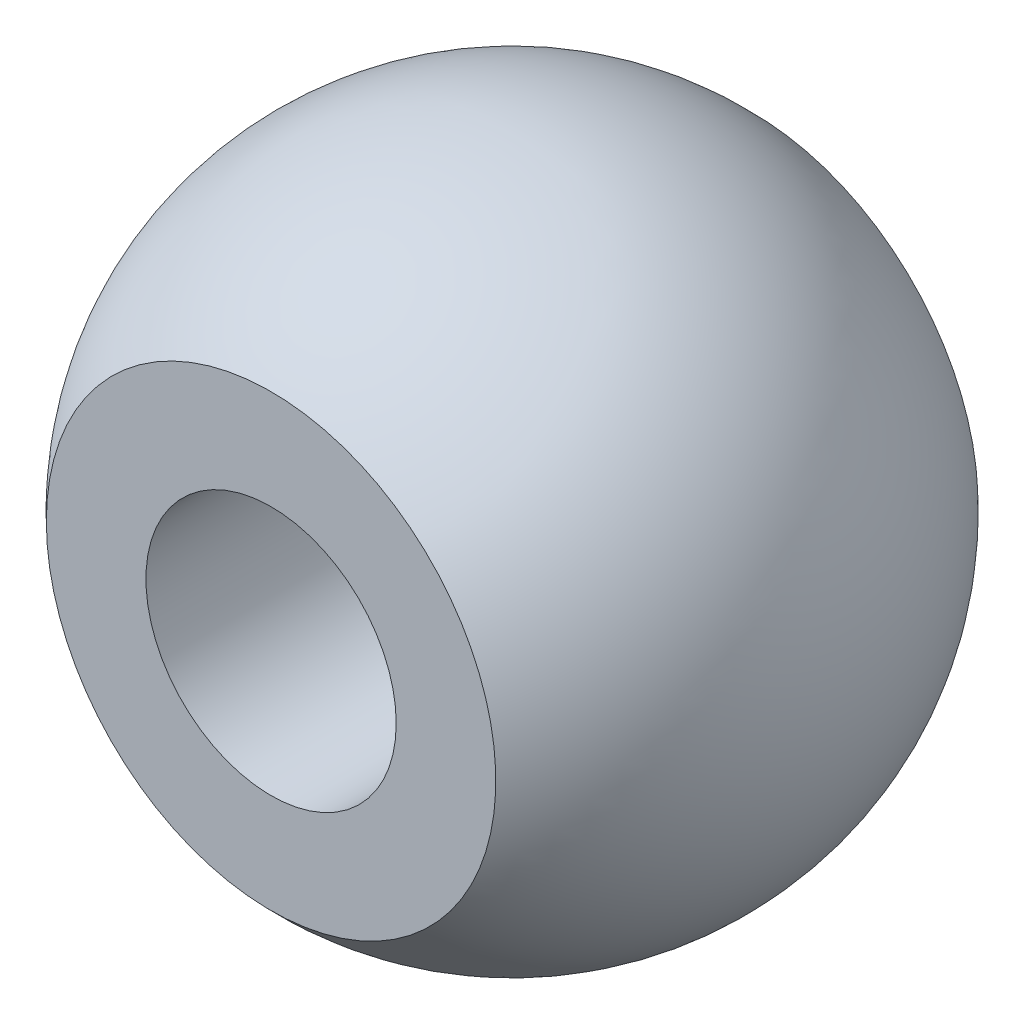
SolidWorks part; units mm, degrees
ref_plane "Front Plane" through (0, 0, 0) normal (0, 0, 1) x (1, 0, 0)
ref_plane "Top Plane" through (0, 0, 0) normal (0, 1, 0) x (1, 0, 0)
ref_plane "Right Plane" through (0, 0, 0) normal (1, 0, 0) x (0, 0, -1)
ref_axis "X Axis" through (-88.99, 0, 0) along (1, 0, 0)
ref_axis "Y Axiz" through (0, 0, 55) along (0, 0, -1)
ref_axis "Z Axis" through (0, 55, 0) along (0, -1, 0)
sketch "Sketch1" plane through (0, 0, 0) normal (0, 1, 0) x (1, 0, 0)
  line L0 (0, -3.95) -> (0, 3.95) construction
  line L1 (0, -3.95) -> (0, 3.95)
  arc A1 (0, -3.95) -> (0, 3.95) centre (0, 0) ccw
  dimension "D1" = 7.9
revolve "Revolve4" add sketch "Sketch1" angle 360 about L0
sketch "Sketch2" plane through (0, 0, 0) normal (0, 1, 0) x (1, 0, 0)
  line L1 (-3.95, -3.95) -> (3.95, -3.95)
  line L2 (-3.95, -3.95) -> (-3.95, 3.95)
  line L3 (-3.95, 3.95) -> (3.95, 3.95)
  line L4 (3.95, -3.95) -> (3.95, 3.95)
  line L5 (-3.95, -3.95) -> (3.95, 3.95) construction
  line L6 (-3.95, 3.95) -> (3.95, -3.95) construction
  line L7 (-3.95, -2.889) -> (3.95, -2.889)
  line L8 (-3.95, -2.889) -> (-3.95, 2.889)
  line L9 (-3.95, 2.889) -> (3.95, 2.889)
  line L10 (3.95, -2.889) -> (3.95, 2.889)
  line L11 (-3.95, -2.889) -> (3.95, 2.889) construction
  line L12 (-3.95, 2.889) -> (3.95, -2.889) construction
  point P0 (0, 0)
  point P5 (0, 0)
  dimension "D1" = 7.9
  dimension "D2" = 5.7781
  dimension "D3" = 7.9
extrude "Cut-Extrude1" cut sketch "Sketch2" against normal through all and the other way through all contours L7 L2 L1 L4 | L2 L9 L4 L3 region at (0, 0, 3.4195) region at (0, 0, -3.4195)
sketch "Sketch3" plane through (0, 0, 2.889) normal (0, 0, 1) x (1, 0, 0)
  circle A0 centre (0, 0) radius 1.5
  dimension "D1" = 3
extrude "Cut-Extrude2" cut sketch "Sketch3" against normal through all
ref_point "Point2"
